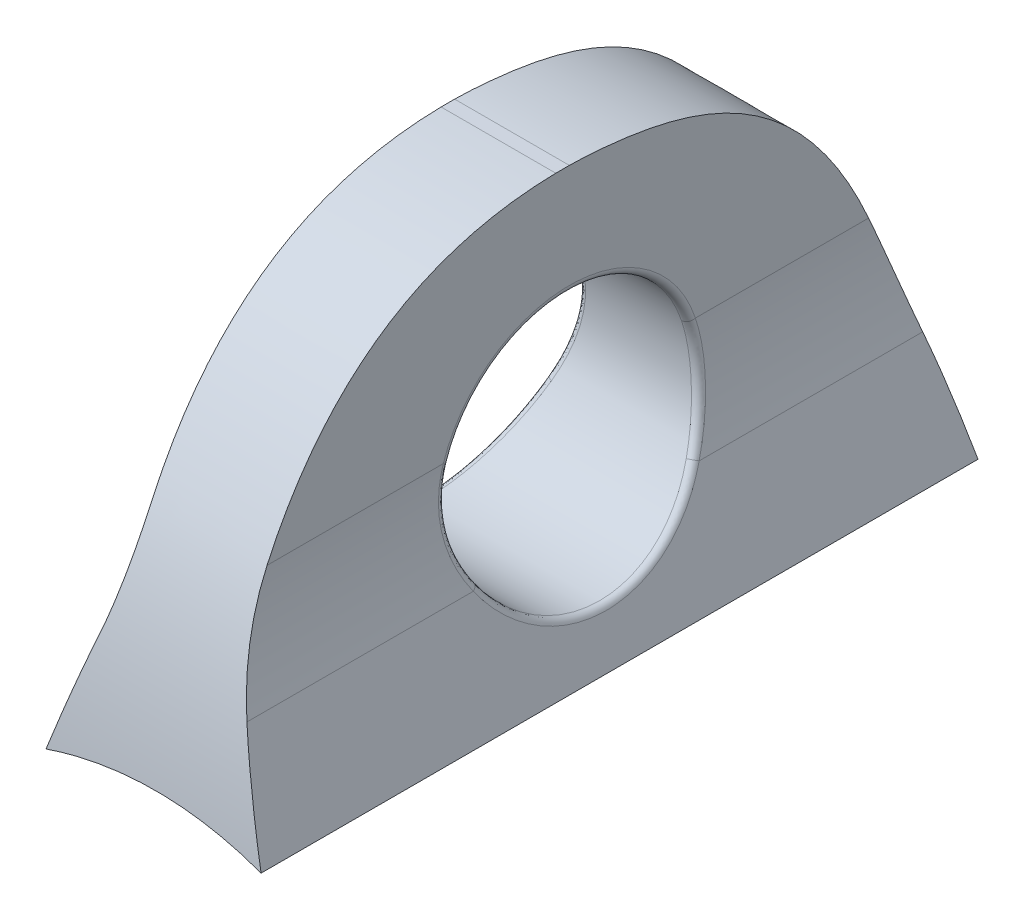
SolidWorks part; units mm, degrees
ref_plane "Front Plane" through (0, 0, 0) normal (0, 0, 1) x (1, 0, 0)
ref_plane "Top Plane" through (0, 0, 0) normal (0, 1, 0) x (1, 0, 0)
ref_plane "Right Plane" through (0, 0, 0) normal (1, 0, 0) x (0, 0, -1)
sketch "Sketch1" plane through (0, 0, 0) normal (0, 0, 1) x (1, 0, 0)
  line L0 (-8, 29.9355) -> (8, 29.9355)
  line L1 (8, 29.9355) -> (8, -5.0645)
  line L2 (8, -5.0645) -> (15, -27.0645)
  line L3 (15, -27.0645) -> (-15, -27.0645)
  line L5 (-8, -5.0645) -> (-15, -27.0645)
  line L6 (-8, 29.9355) -> (-8, -5.0645)
  dimension "D1" = 30
  dimension "D2" = 16
  dimension "D4" = 35
extrude "Boss-Extrude1" add sketch "Sketch1" against normal blind 100
ref_plane "Plane1" through (20, 0, 0) normal (1, 0, 0) x (0, 0, -1)
sketch "Sketch2" plane through (20, 0, 0) normal (1, 0, 0) x (0, 0, -1)
  line L0 (0, -27.0645) -> (100, -27.0645)
  line L1 (100, 29.9355) -> (0, 29.9355) construction
  circle A0 centre (50, -3.0645) radius 17.5
  spline S0 degree 3 poles (100, -27.0645) (92.4013, 18.6861) (71.0416, 29.319) (31.5544, 30.6732) (5.7329, 17.6855) (0, -27.0645) knots 0 0 0 0 0.474066 0.574066 1 1 1 1
  dimension "D1" = 35
  dimension "D2" = 24
extrude "Cut-Extrude1" cut sketch "Sketch2" against normal blind 100 flip side to cut
fillet "Fillet1" radius 50 4 edges at (8, -5.0645, -18.7041) (-8, -5.0645, -81.0621) (8, -5.0645, -81.0621) (-8, -5.0645, -18.7041)
fillet "Fillet2" radius 1 8 edges at (-8, 14.4355, -50) (8, 14.4355, -50) (8.306, -2.8253, -32.5016) (-8.306, -2.8253, -67.4984) (8.9757, -7.1313, -67.0209) (12.9318, -20.5645, -50) (-8.9757, -7.1313, -32.9791) (-12.9318, -20.5645, -50)
ref_plane "Plane2" through (0, 0, 20) normal (0, 0, 1) x (1, 0, 0)
sketch "Sketch3" plane through (0, 0, 20) normal (0, 0, 1) x (1, 0, 0)
  circle A0 centre (0, -74.7615) radius 50
  dimension "D1" = 100
extrude "Cut-Extrude2" cut sketch "Sketch3" against normal blind 165
